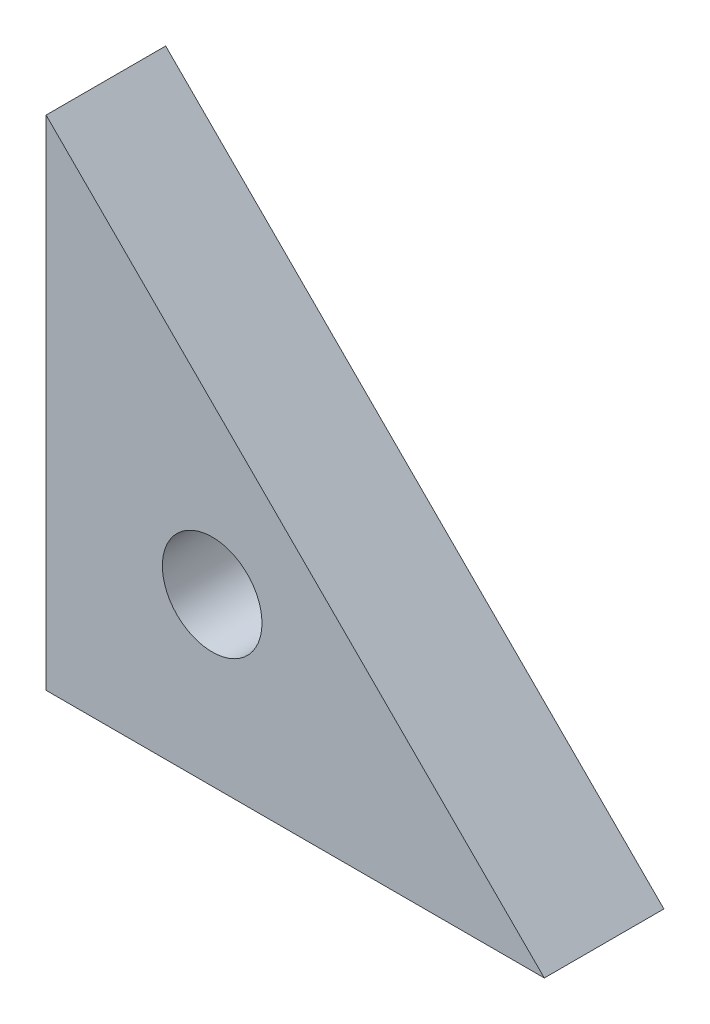
SolidWorks part; units mm, degrees
note: The reader was unsure of these and kept them because the rebuilt part matched: thickness of "Tôle de base pliée1", "Tôlerie1", "Tôlerie2".
material "ASTM A36 Acier"
ref_plane "Front" through (0, 0, 0) normal (0, 0, 1) x (1, 0, 0)
ref_plane "Top" through (0, 0, 0) normal (0, 1, 0) x (1, 0, 0)
ref_plane "Right" through (0, 0, 0) normal (1, 0, 0) x (0, 0, -1)
sketch "Esquisse2" plane through (0, 0, 0) normal (0, 0, 1) x (1, 0, 0)
  line L0 (0, 0) -> (0, 25)
  line L1 (0, 25) -> (25, 0)
  line L2 (25, 0) -> (0, 0)
  line L3 (0, 8.3333) -> (8.3333, 8.3333) construction
  line L4 (8.3333, 8.3333) -> (8.3333, 0) construction
  dimension "D3" = 8.3333
  dimension "D1" = 45
  dimension "D2" = 25
  dimension "D4" = 8.3333
base flange "Tôle de base pliée1" sketch "Esquisse2" thickness 6 reverse thickness direction no parameters "D1"=0.7366
hole_wizard "Trou taraudé M61" positions "Esquisse7" profile "Esquisse8" tap size "M6" standard "ISO" end condition through all
sketch "Esquisse7" plane through (0, 0, 0) normal (0, 0, 1) x (1, 0, 0)
  point P0 (8.3333, 8.3333)
sketch "Esquisse8" plane through (8.3333, 8.3333, 0) normal (1, 0, 0) x (0, -1, 0)
  line L0 (0, 0) -> (0, 6)
  line L1 (0, 6) -> (2.5, 6)
  line L2 (2.5, 6) -> (2.5, 0)
  line L5 (2.5, 0) -> (0, 0)
  line L11 (0, -6.35) -> (0, 107.95) construction
  dimension "Diamètre du trou pour taraudage jusqu'au prochain" = 5
  dimension "Profondeur du trou pour taraudage jusqu'au prochain" = 6
cosmetic thread "Filetage de perçage1"
sketch "Lignes de pliage1" [suppressed] plane through (0, 0, 0) normal (0, 1, 0) x (1, 0, 0)
sketch "Cube de visualisation1" [suppressed] plane through (0, 0, 0) normal (0, 1, 0) x (1, 0, 0)
sheet metal parameters "Tôlerie1" thickness 6 parameters "D1"=0.7366
flat pattern "Etat déplié1" [suppressed]
sketch "Lignes de pliage2" plane through (0, 0, 0) normal (0, 1, 0) x (1, 0, 0)
sketch3d "Cube de visualisation2" [suppressed]
  line L0 (0, 0, 0) -> (-25, 0, 0) construction
  line L1 (0, 25, 0) -> (-25, 25, 0) construction
  line L2 (0, 0, 0) -> (0, 25, 0) construction
  line L3 (-25, 0, 0) -> (-25, 25, 0) construction
sheet metal parameters "Tôlerie2" thickness 6 parameters "D1"=0.7366, "D7"=5
flat pattern "Etat déplié1"
sketch "Lignes de pliage2" plane through (0, 0, 0) normal (0, 1, 0) x (1, 0, 0)
sketch3d "Cube de visualisation2" [suppressed]
  line L0 (0, 0, 0) -> (25, 0, 0) construction
  line L1 (0, 25, 0) -> (25, 25, 0) construction
  line L2 (0, 0, 0) -> (0, 25, 0) construction
  line L3 (25, 0, 0) -> (25, 25, 0) construction
